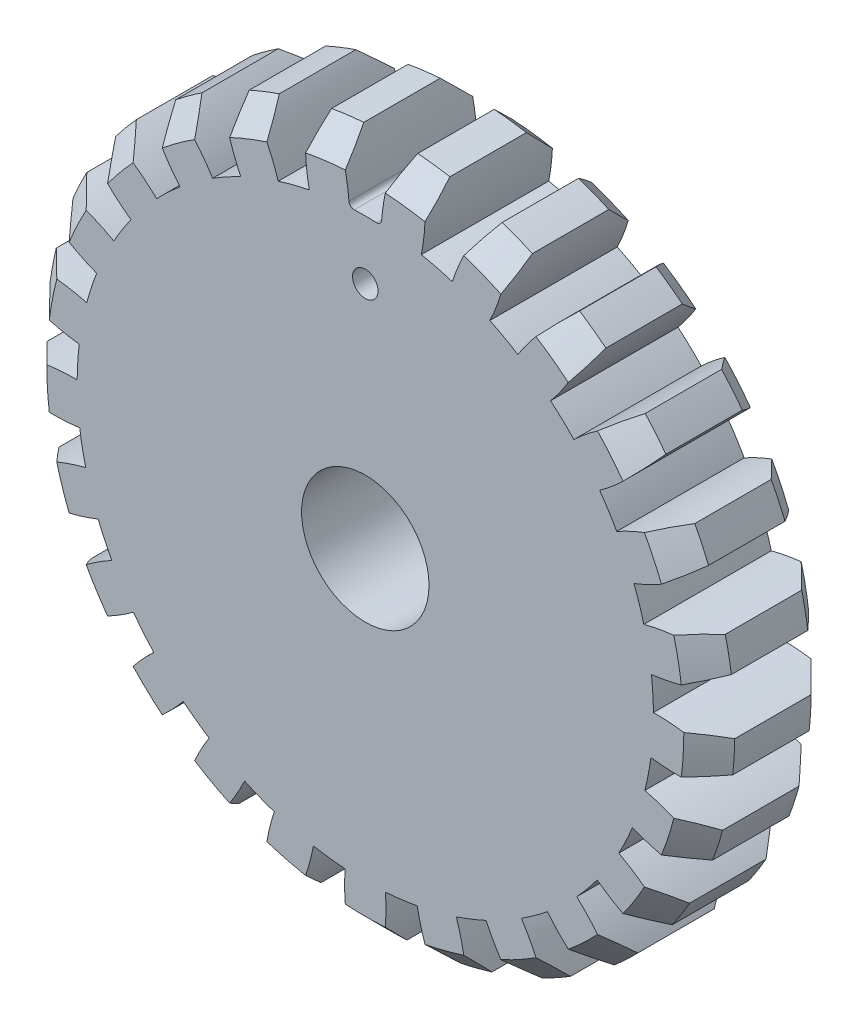
SolidWorks part; units mm, degrees
note: The reader was unsure of these and kept them because the rebuilt part matched: shared geometry of "Sketch1<3>", "Sketch1<4>".
ref_plane "Front Plane" through (0, 0, 0) normal (0, 0, 1) x (1, 0, 0)
ref_plane "Top Plane" through (0, 0, 0) normal (0, 1, 0) x (1, 0, 0)
ref_plane "Right Plane" through (0, 0, 0) normal (1, 0, 0) x (0, 0, -1)
sketch "Sketch1" plane through (0, 0, 0) normal (0, 0, 1) x (1, 0, 0)
  line L0 (0, 0) -> (0, 27) construction
  line L1 (0, 0) -> (6.7146, 26.1517) construction
  line L2 (0, 0) -> (3.384, 26.7871) construction
  line L3 (-1.2566, 22.5789) -> (0, 0) construction
  line L4 (-1.5698, 24.9507) -> (1.5698, 24.9507) construction
  line L5 (1.5698, 24.9507) -> (4.6845, 24.5572) construction
  line L6 (-1.9847, 26.927) -> (0, 17.4739) construction
  circle A0 centre (0, 0) radius 25 construction
  circle A1 centre (0, 0) radius 27
  circle A2 centre (0, 0) radius 23
  arc A4 (-2.1171, 26.9169) -> (-1.2566, 22.5789) centre (-17.0542, 21.6997) cw
  arc A5 (2.1171, 26.9169) -> (1.2566, 22.5789) centre (17.0542, 21.6997) ccw
  arc A6 (1.2566, 22.5789) -> (-1.2566, 22.5789) centre (0, 0) ccw
  circle A7 centre (0, 0) radius 5
  dimension "D1" = 50
  dimension "D5" = 54
  dimension "D4" = 10
  dimension "D3" = 14.4
  dimension "D2" = 4
extrude "Boss-Extrude1" add sketch "Sketch1" along normal mid plane 10 contours A1
extrude "Cut-Extrude1" cut sketch "Sketch1<3>" against normal through all both and the other way through all contours A5 A6 A4
sketch "Sketch1<3>" plane through (0, 0, 0) normal (0, 0, 1) x (1, 0, 0) same geometry as "Sketch1"
fillet "Fillet1" radius 0.4 2 edges at (1.2566, 22.5789, 0) (-1.2566, 22.5789, 0)
chamfer "Chamfer1" distance 2 angle 45 2 edges at (0, -27, -5) (0, -27, 5)
pattern_circular "CirPattern26" count 25 over 360 about axis through (0, 0, 5) along (0, 0, -1) of "Cut-Extrude1"
extrude "Cut-Extrude2" cut sketch "Sketch1<4>" against normal through all both and the other way through all contours A7
sketch "Sketch1<4>" plane through (0, 0, 0) normal (0, 0, 1) x (1, 0, 0) same geometry as "Sketch1"
sketch "Sketch6" plane through (0, 0, -5) normal (0, 0, -1) x (-1, 0, 0)
  line L1 (0, 0) -> (0, 27) construction
  circle A2 centre (0, 18) radius 1
  dimension "D2" = 2
  dimension "D1" = 18
extrude "Cut-Extrude3" cut sketch "Sketch6" against normal through all both and the other way through all
equation "\"Module\"= 2mm"
equation "\"Number of teeth\"= 25"
equation "\"Pressure angle\"= 20"
equation "\"D1@Sketch1\"=\"Module\" *\"Number of teeth\""
equation "\"D3@Sketch1\"= 360  /\"Number of teeth\""
equation "\"D2@Sketch1\"=\"Module\" * 2"
equation "\"D1@Fillet1\"=0.2 * \"Module\""
